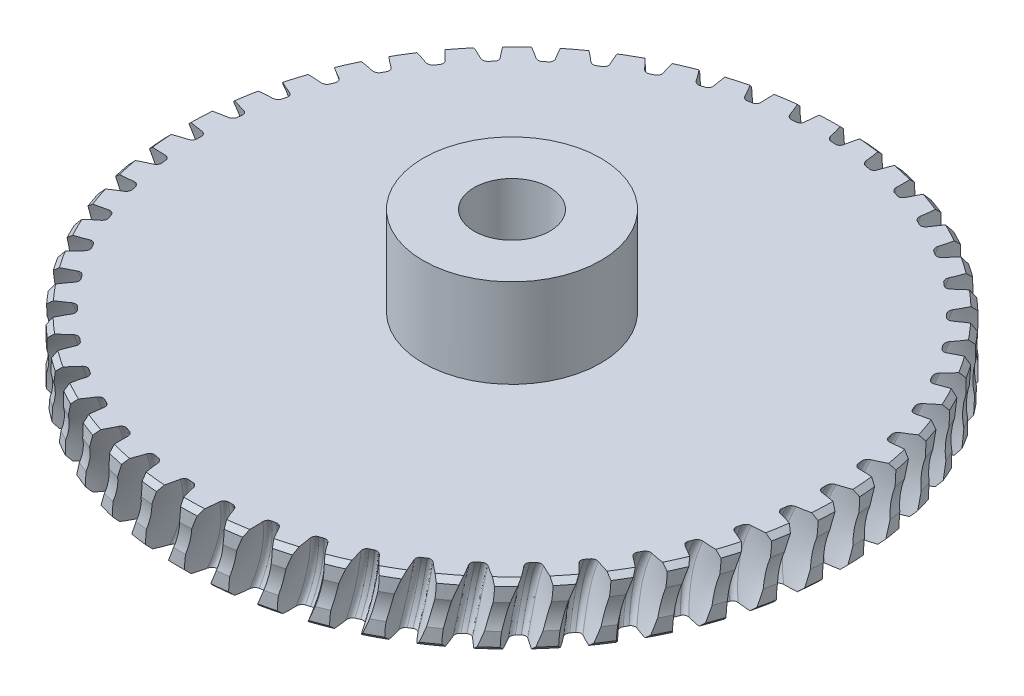
SolidWorks part; units mm, degrees
note: '?' marks a value the reader was unsure of.
ref_plane "Front" through (0, 0, 0) normal (0, 0, 1) x (1, 0, 0)
ref_plane "Top" through (0, 0, 0) normal (0, 1, 0) x (1, 0, 0)
ref_plane "Right" through (0, 0, 0) normal (1, 0, 0) x (0, 0, -1)
sketch "wormGear" plane through (0, 0, 0) normal (0, 0, 1) x (1, 0, 0)
  line L0 (0, -3.937) -> (0, 3.937)
  line L1 (0, 3.937) -> (-40.85, 3.937)
  line L2 (-41.4734, 3.3136) -> (-41.4734, 1.575)
  line L3 (0, 0) -> (-40.9575, 0) construction
  line L4 (0, -3.937) -> (-40.85, -3.937)
  line L5 (-40.85, -3.937) -> (-41.4734, -3.3136)
  line L6 (-40.85, 3.937) -> (-41.4734, 3.3136)
  line L7 (-41.4734, -1.575) -> (-41.4734, -3.3136)
  arc A0 (-41.4734, -1.575) -> (-41.4734, 1.575) centre (-47.625, 0) ccw
  point P3 (-41.4734, -3.937)
  point P4 (-41.4734, 3.937)
  dimension "throatDiameter" = 12.7
  dimension "face" = 7.874
  dimension "od" = 41.4734
  dimension "cd" = 47.625
  dimension "toothChamfer1" = 0.6234
  dimension "toothChamfer2" = 0.6234
ref_axis "Axis1" through (0, 0, 0) along (0, 1, 0)
ref_axis "Axis2" through (0, 0, 0) along (-1, 0, 0)?
revolve "Revolve1" add sketch "wormGear" angle 360 about L0
ref_plane "offsetPlane" through (0, 0, -2.4936) normal (0, 0, 1) x (1, 0, 0)
ref_plane "offsetPlaneLH" through (0, 0, 2.4936) normal (0, 0, 1) x (1, 0, 0)
sketch "worm" plane through (0, 0, -2.4936) normal (0, 0, 1) x (1, 0, 0)
  circle A0 centre (-47.625, 0) radius 7.9375
  dimension "pd" = 15.875
  dimension "cd" = 47.625
ref_axis "Axis3" through (-47.625, 0, 71.7568) along (0, 0, -1)?
ref_plane "toothCutPlane" through (-47.625, 0, 0) normal (1, 0, 0) x (0, 0, -1)
sketch "toothCut1" plane through (-47.625, 0, 0) normal (1, 0, 0) x (0, 0, -1)
  line L0 (3.7403, -7.9571) -> (18.7252, -12.7984) construction
  line L1 (2.4936, -47.625) -> (2.4936, -7.9375) construction
  line L2 (2.4936, -47.625) -> (3.7403, -7.9571) construction
  line L3 (2.4936, 0) -> (2.4936, -47.625) construction
  line L4 (2.4936, 7.9375) -> (2.4936, -7.9375) construction
  arc A0 (2.7611, -9.7752) -> (2.2262, -9.7752) centre (2.4936, -47.625) ccw
  circle A1 centre (2.4936, -47.625) radius 38.4234 construction
  circle A2 centre (2.4936, -47.625) radius 39.6875 construction
  circle A3 centre (2.4936, -47.625) radius 41.275 construction
  arc A4 (4.8911, -5.2748) -> (0.0962, -5.2748) centre (2.4936, -47.625) ccw
  arc A5 (4.8911, -5.2748) -> (3.3732, -9.2907) centre (18.7252, -12.7984) ccw
  arc A6 (2.7611, -9.7752) -> (3.3732, -9.2907) centre (2.7655, -9.1518) ccw
  arc A7 (2.2262, -9.7752) -> (1.614, -9.2907) centre (2.2218, -9.1518) cw
  arc A8 (0.0962, -5.2748) -> (1.614, -9.2907) centre (-13.738, -12.7984) cw
  dimension "minorDiameter" = 75.7015
  dimension "baseDia" = 76.8467
  dimension "pd" = 79.375
  dimension "od" = 82.55
  dimension "overOD" = 84.836
  dimension "flankRadius2" = 15.7476
  dimension "rFillet" = 0.6234
  dimension "toothAng" = 1.8
  dimension "cd" = 47.625
  dimension "flankRadius" = 15.7476
sketch "Sketch1" plane through (0, 0, -2.4936) normal (0, 0, 1) x (1, 0, 0)
  circle A0 centre (-47.625, 0) radius 14.5161
  dimension "D1" = 29.0322
curve "Helix/Spiral1" pitch 9.9746 height 4.9873 turns 0.5 parameters "height"=4.9873, "pitch"=9.9746
sweep "Cut-Sweep5" cut profiles "toothCut1" path "Helix/Spiral1"
pattern_circular "CirPattern1" count 50 over 360 about axis through (0, 0, 0) along (0, 1, 0) of "Cut-Sweep5"
sketch "hubSketch1" plane through (0, 3.937, 0) normal (0, 1, 0) x (-1, 0, 0)
  circle A0 centre (0, 0) radius 11.176
  dimension "hubDiameter1" = 22.352
extrude "hub1" add sketch "hubSketch1" along normal blind 11.176
sketch "hubSketch2" plane through (0, -3.937, 0) normal (0, -1, 0) x (1, 0, 0)
  circle A0 centre (0, 0) radius 11.176
  dimension "hubdiameter2" = 22.352
sketch "boreSketch" plane through (0, 0, 0) normal (0, 1, 0) x (1, 0, 0)
  circle A0 centre (0, 0) radius 4.7625
  dimension "boreDiameter" = 9.525
extrude "bore" cut sketch "boreSketch" against normal mid plane 25400
sketch "toothCut2" plane through (-47.625, 0, 0) normal (1, 0, 0) x (0, 0, -1)
  line L0 (-1.247, -7.9571) -> (13.738, -12.7984) construction
  line L1 (-2.4936, -47.625) -> (-2.4936, -7.9375) construction
  line L2 (-2.4936, -47.625) -> (-1.247, -7.9571) construction
  line L3 (-2.4936, 0) -> (-2.4936, -47.625) construction
  line L4 (-2.4936, 50) -> (-2.4936, -50) construction
  line L9 (-71.7568, 0) -> (-8.988, 0) construction
  arc A0 (-2.2262, -9.7752) -> (-2.7611, -9.7752) centre (-2.4936, -47.625) ccw
  circle A1 centre (-2.4936, -47.625) radius 38.4234 construction
  circle A2 centre (-2.4936, -47.625) radius 39.6875 construction
  circle A3 centre (-2.4936, -47.625) radius 41.275 construction
  arc A4 (-0.0962, -5.2748) -> (-4.8911, -5.2748) centre (-2.4936, -47.625) ccw
  arc A5 (-0.0962, -5.2748) -> (-1.614, -9.2907) centre (13.738, -12.7984) ccw
  arc A6 (-2.2262, -9.7752) -> (-1.614, -9.2907) centre (-2.2218, -9.1518) ccw
  arc A7 (-2.7611, -9.7752) -> (-3.3732, -9.2907) centre (-2.7655, -9.1518) cw
  arc A8 (-4.8911, -5.2748) -> (-3.3732, -9.2907) centre (-18.7252, -12.7984) cw
  dimension "minorDiameter" = 75.7015
  dimension "baseDia" = 76.8467
  dimension "pd" = 79.375
  dimension "od" = 82.55
  dimension "overOD" = 84.836
  dimension "flankRadius2" = 15.7476
  dimension "rFillet" = 0.6234
  dimension "toothAng" = 1.8
  dimension "cd" = 47.625
  dimension "flankRadius" = 15.7476
sketch "Sketch3" plane through (0, 0, 2.4936) normal (0, 0, 1) x (1, 0, 0)
  circle A0 centre (-47.625, 0) radius 14.5161
  dimension "D1" = 29.0322
curve "Helix/Spiral2" pitch 9.9746 height 4.9873 turns 0.5 parameters "height"=4.9873, "pitch"=9.9746
